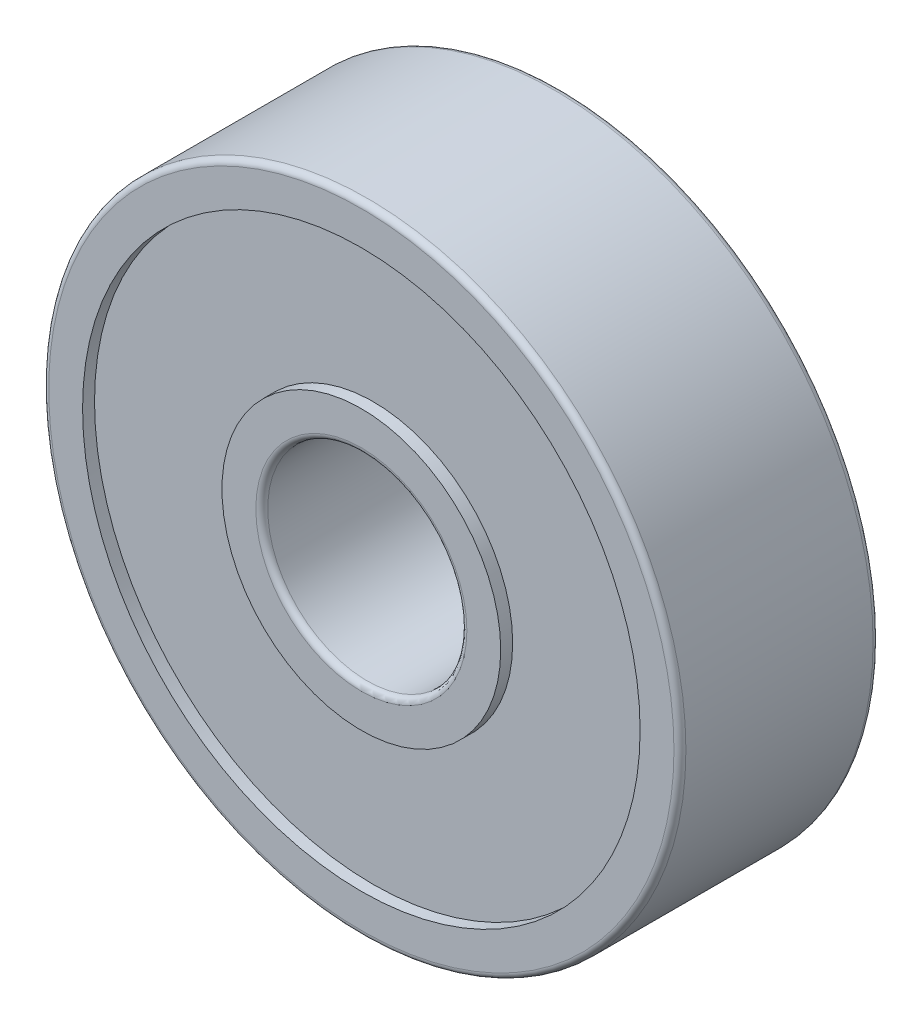
SolidWorks part; units mm, degrees
ref_plane "Front Plane" through (0, 0, 0) normal (0, 0, 1) x (1, 0, 0)
ref_plane "Top Plane" through (0, 0, 0) normal (0, 1, 0) x (1, 0, 0)
ref_plane "Right Plane" through (0, 0, 0) normal (1, 0, 0) x (0, 0, -1)
sketch "Sketch1" plane through (0, 0, 0) normal (0, 0, 1) x (1, 0, 0)
  circle A0 centre (0, 0) radius 2.5
  circle A1 centre (0, 0) radius 8
  dimension "D1" = 5
  dimension "D2" = 16
extrude "Boss-Extrude1" add sketch "Sketch1" along normal blind 5
sketch "Sketch2" plane through (0, 0, 5) normal (0, 0, 1) x (1, 0, 0)
  circle A0 centre (0, 0) radius 8 construction
  circle A2 centre (0, 0) radius 2.5 construction
  circle A3 centre (0, 0) radius 7
  circle A6 centre (0, 0) radius 3.5
  dimension "D1" = 1
  dimension "D2" = 1
extrude "Cut-Extrude1" cut sketch "Sketch2" against normal blind 0.3
extrude "Cut-Extrude2" cut sketch "Sketch2<2>" along normal blind 0.5 from surface starting at face at (8, 0, 0)
sketch "Sketch2<2>" plane through (0, 0, 5) normal (0, 0, 1) x (1, 0, 0) same geometry as "Sketch2"
fillet "Fillet1" radius 0.15 4 edges at (2.5, 0, 5) (8, 0, 5) (2.5, 0, 0) (8, 0, 0)
